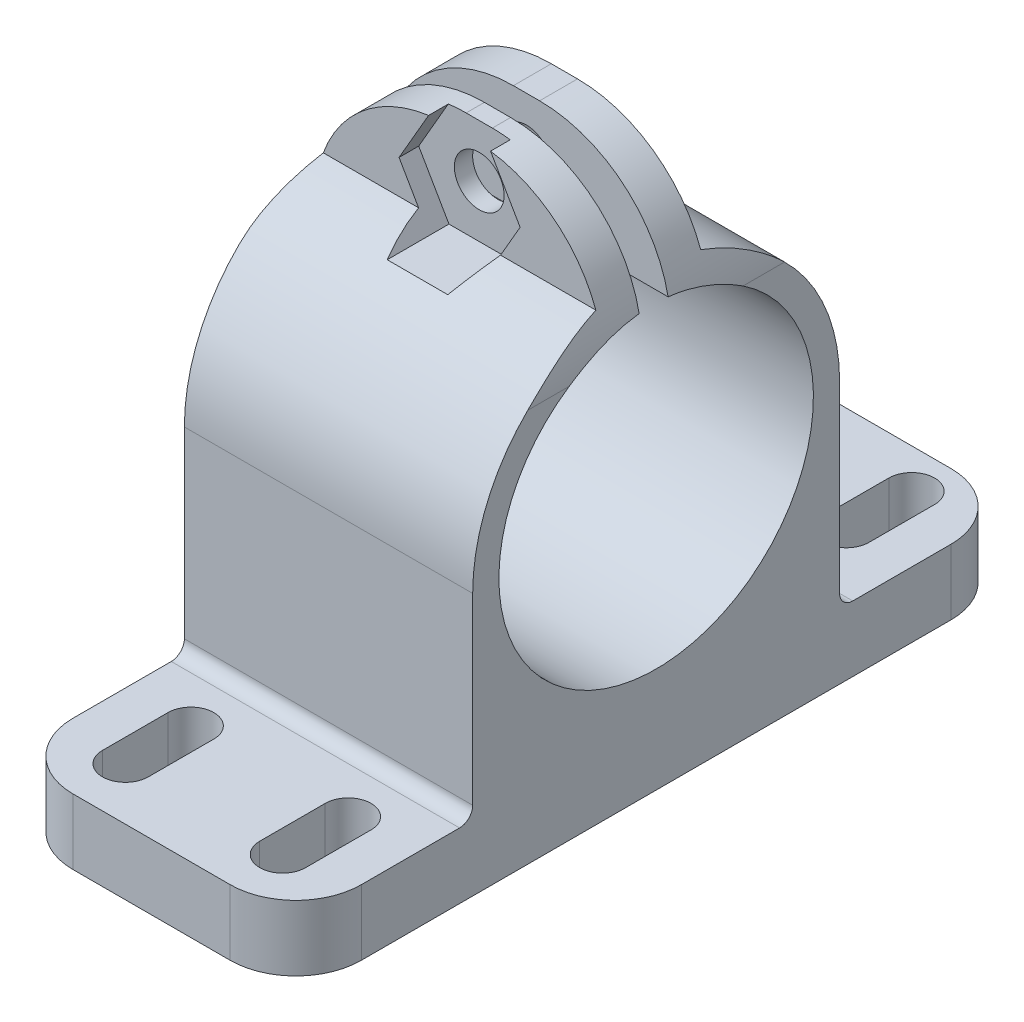
SolidWorks part; units mm, degrees
material "ABS"
ref_plane "Front Plane" through (0, 0, 0) normal (0, 0, 1) x (1, 0, 0)
ref_plane "Top Plane" through (0, 0, 0) normal (0, 1, 0) x (1, 0, 0)
ref_plane "Right Plane" through (0, 0, 0) normal (1, 0, 0) x (0, 0, -1)
sketch "Sketch1" plane through (0, 0, 0) normal (0, 1, 0) x (1, 0, 0)
  line L1 (0, -27.5) -> (-22, -27.5)
  line L2 (0, -27.5) -> (0, 27.5)
  line L3 (0, 27.5) -> (-22, 27.5)
  line L4 (-22, -27.5) -> (-22, 27.5)
  point P4 (0, 0)
  dimension "D1" = 22
  dimension "55" = 55
extrude "Base" add sketch "Sketch1" along normal blind 5
sketch "Sketch2" plane through (0, 0, 0) normal (1, 0, 0) x (0, 0, -1)
  line L0 (-14, 20) -> (-14, 0)
  line L1 (-27.5, 0) -> (27.5, 0) construction
  line L2 (-14, 0) -> (14, 0)
  line L3 (14, 0) -> (14, 20)
  line L4 (0, 19.25) -> (0, -19.25) construction
  circle A0 centre (0, 20) radius 12
  arc A1 (14, 20) -> (-14, 20) centre (0, 20) ccw
  dimension "D1" = 24
  dimension "D2" = 20
  dimension "D3" = 28
extrude "Motor Support" add sketch "Sketch2" against normal blind 22
sketch "Sketch3" plane through (0, 0, 0) normal (1, 0, 0) x (0, 0, -1)
  line L1 (-4, 32) -> (4, 32)
  line L2 (-4, 32) -> (-4, 40)
  line L3 (-4, 40) -> (4, 40)
  line L4 (4, 32) -> (4, 40)
  line L6 (0, 2.75) -> (0, -2.75) construction
  circle A1 centre (0, 20) radius 12 construction
  point P4 (0, 32)
  dimension "D1" = 8
  dimension "D2" = 8
extrude "Clamp Flange" add sketch "Sketch3" against normal blind 22
sketch "Sketch4" plane through (0, 0, 0) normal (1, 0, 0) x (0, 0, -1)
  line L0 (0, 19.25) -> (0, -19.25) construction
  line L1 (-1.1042, 41) -> (1.1042, 41)
  line L2 (-1.1042, 41) -> (-1.1042, 26)
  line L3 (-1.1042, 26) -> (1.1042, 26)
  line L4 (1.1042, 41) -> (1.1042, 26)
  line L5 (-1.1042, 41) -> (1.1042, 26) construction
  line L6 (-1.1042, 26) -> (1.1042, 41) construction
  line L7 (4, 40) -> (-4, 40) construction
  point P0 (0, 33.5)
  dimension "D1" = 2.2084
  dimension "D2" = 15
  dimension "D3" = 1
extrude "Slot" cut sketch "Sketch4" against normal blind 35
hole_wizard "#6 Clearance Hole1" positions "Sketch6" profile "Sketch5" hole size "#6" standard "ANSI Inch" end condition through all
sketch "Sketch6" plane through (0, 0, 4) normal (0, 0, 1) x (1, 0, 0)
  line L0 (0, 40) -> (0, 33.4164) construction
  line L1 (-22, 40) -> (0, 40) construction
  point P0 (-11, 36)
  dimension "D1" = 11
  dimension "D2" = 4
sketch "Sketch5" plane through (-11, 36, 4) normal (1, 0, 0) x (0, -1, 0)
  line L0 (0, 0) -> (0, 31.5)
  line L1 (0, 31.5) -> (1.8986, 31.5)
  line L2 (1.8986, 31.5) -> (1.8986, 0)
  line L5 (1.8986, 0) -> (0, 0)
  line L11 (0, -6.35) -> (0, 107.95) construction
  dimension "Thru Hole Dia." = 3.7973
  dimension "Thru Hole Depth" = 31.5
sketch "Sketch7" plane through (0, 0, 4) normal (0, 0, 1) x (1, 0, 0)
  line L0 (-22, 40) -> (0, 40) construction
  line L1 (-8.6906, 40) -> (-13.3094, 40)
  line L2 (-13.3094, 40) -> (-15.6188, 36)
  line L3 (-15.6188, 36) -> (-13.3094, 32)
  line L4 (-13.3094, 32) -> (-8.6906, 32)
  line L5 (-8.6906, 32) -> (-6.3812, 36)
  line L6 (-6.3812, 36) -> (-8.6906, 40)
  circle A0 centre (-11, 36) radius 4 construction
  dimension "D1" = 8
extrude "Hex-Cut" cut sketch "Sketch7" against normal blind 1.5 and the other way through all
sketch "Sketch9" plane through (0, 0, -4) normal (0, 0, -1) x (-1, 0, 0)
  circle A0 centre (11, 36) radius 3.5
  dimension "D1" = 7
extrude "Screw Head Cut" cut sketch "Sketch9" along normal through all
sketch "Sketch8" plane through (0, 5, 0) normal (0, 1, 0) x (1, 0, 0)
  line L0 (-17, 19.5) -> (-17, 24.5) construction
  line L1 (-18.75, 19.5) -> (-18.75, 24.5)
  line L2 (-15.25, 19.5) -> (-15.25, 24.5)
  line L3 (0, 27.5) -> (-22, 27.5) construction
  line L4 (-22, 27.5) -> (-22, 14) construction
  arc A0 (-18.75, 19.5) -> (-15.25, 19.5) centre (-17, 19.5) ccw
  arc A1 (-15.25, 24.5) -> (-18.75, 24.5) centre (-17, 24.5) ccw
  point P2 (-17, 22)
  dimension "D1" = 3.5
  dimension "D2" = 5
  dimension "D3" = 3
  dimension "D4" = 5
extrude "Mounting Slot" cut sketch "Sketch8" against normal through all
pattern_linear "LPattern1" count 2 spacing 12 along (1, 0, 0) count 2 spacing 43 along (0, 0, 1) of "Mounting Slot"
fillet "Fillet2" radius 5 4 edges at (-22, 2.5, -27.5) (0, 2.5, -27.5) (-22, 2.5, 27.5) (0, 2.5, 27.5)
fillet "Fillet3" radius 1 2 edges at (-11, 5, 14) (-11, 5, -14)
fillet "Fillet4" radius 10 4 edges at (-22, 40, -2.5521) (-22, 40, 2.5521) (0, 40, -2.5521) (0, 40, 2.5521)
